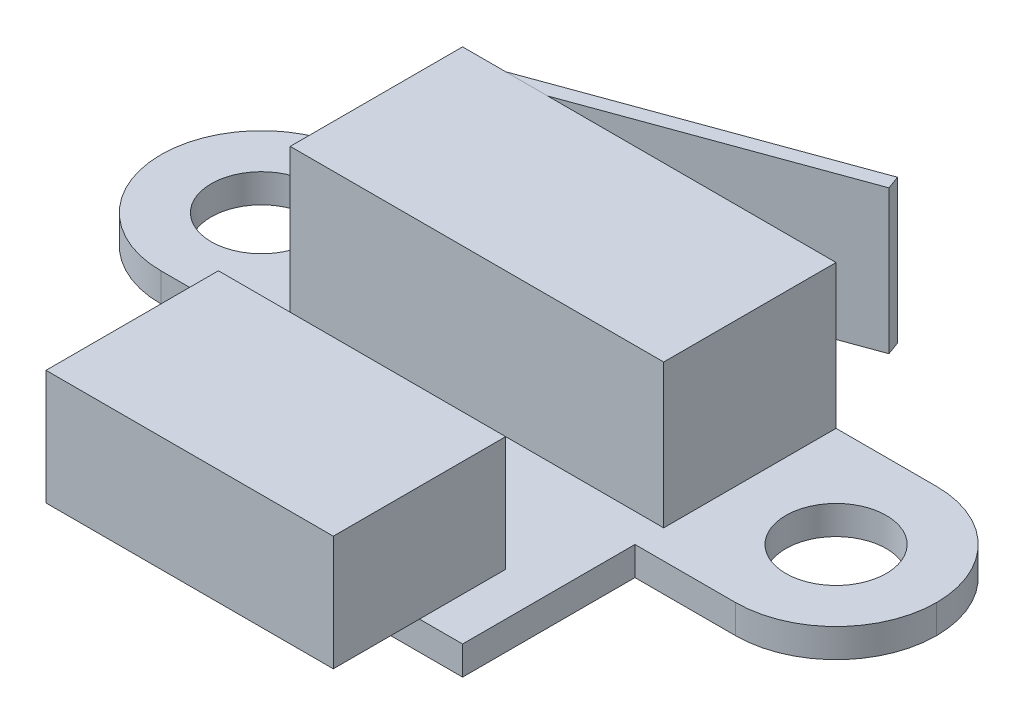
SolidWorks part; units mm, degrees
ref_plane "Front Plane" through (0, 0, 0) normal (0, 0, 1) x (1, 0, 0)
ref_plane "Top Plane" through (0, 0, 0) normal (0, 1, 0) x (1, 0, 0)
ref_plane "Right Plane" through (0, 0, 0) normal (1, 0, 0) x (0, 0, -1)
sketch "Sketch1" plane through (0, 0, 0) normal (0, 1, 0) x (1, 0, 0)
  line L1 (-6.5, -6.5) -> (6.5, -6.5)
  line L2 (-6.5, -6.5) -> (-6.5, 6.5)
  line L3 (-6.5, 6.5) -> (6.5, 6.5)
  line L4 (6.5, -6.5) -> (6.5, 6.5)
  line L5 (-6.5, -6.5) -> (6.5, 6.5) construction
  line L6 (-6.5, 6.5) -> (6.5, -6.5) construction
  point P0 (0, 0)
  dimension "D1" = 13
  dimension "D2" = 13
extrude "Boss-Extrude1" add sketch "Sketch1" along normal blind 1
sketch "Sketch4" plane through (-6.5, 0, 0) normal (-1, 0, 0) x (0, 0, 1)
  line L0 (-6.5, 1) -> (6.5, 1) construction
  line L1 (-6.5, 0) -> (0.5, 0)
  line L2 (-6.5, 0) -> (-6.5, 1)
  line L3 (-6.5, 1) -> (0.5, 1)
  line L4 (0.5, 0) -> (0.5, 1)
  dimension "D1" = 7
extrude "Boss-Extrude2" add sketch "Sketch4" along normal blind 7
sketch "Sketch5" plane through (6.5, 0, 0) normal (1, 0, 0) x (0, 0, -1)
  line L0 (-6.5, 0) -> (6.5, 0) construction
  line L1 (6.5, 1) -> (-0.5, 1)
  line L2 (6.5, 1) -> (6.5, 0)
  line L3 (6.5, 0) -> (-0.5, 0)
  line L4 (-0.5, 1) -> (-0.5, 0)
  dimension "D1" = 7
extrude "Boss-Extrude3" add sketch "Sketch5" along normal blind 7
sketch "Sketch6" plane through (0, 1, 0) normal (0, 1, 0) x (1, 0, 0)
  line L0 (-13.5, -0.5) -> (-6.5, -0.5) construction
  line L2 (-13.5, -0.5) -> (-13.5, 6.5) construction
  circle A0 centre (-10, 3) radius 1.75
  circle A1 centre (10, 3) radius 1.75
  point P10 (13.5, 2.898)
  dimension "D1" = 3.5
  dimension "D4" = 3.5
  dimension "D2" = 3.5
  dimension "D3" = 3.5
  dimension "D5" = 20
extrude "Cut-Extrude1" cut sketch "Sketch6" against normal through all
sketch "Sketch7" plane through (0, 1, 0) normal (0, 1, 0) x (1, 0, 0)
  line L0 (13.5, 6.5) -> (-13.5, 6.5) construction
  line L1 (-5, -3.5) -> (5, -3.5)
  line L2 (-5, -3.5) -> (-5, -9.5)
  line L3 (-5, -9.5) -> (5, -9.5)
  line L4 (5, -3.5) -> (5, -9.5)
  line L5 (-6.5, -0.5) -> (-6.5, -6.5) construction
  dimension "D1" = 6
  dimension "D2" = 10
  dimension "D3" = 10
  dimension "D4" = 1.5
extrude "Boss-Extrude4" add sketch "Sketch7" along normal blind 4
sketch "Sketch8" plane through (0, 1, 0) normal (0, 1, 0) x (1, 0, 0)
  line L0 (-6.5, -0.5) -> (-6.5, -6.5) construction
  line L1 (-6.5, 0.5) -> (6.5, 0.5)
  line L2 (-6.5, 0.5) -> (-6.5, 6.5)
  line L3 (-6.5, 6.5) -> (6.5, 6.5)
  line L4 (6.5, 0.5) -> (6.5, 6.5)
  line L5 (13.5, 6.5) -> (-13.5, 6.5) construction
  dimension "D1" = 13
  dimension "D2" = 0
  dimension "D3" = 6
  dimension "D4" = 0
extrude "Boss-Extrude5" add sketch "Sketch8" along normal blind 5
sketch "Sketch12" plane through (0, 6, 0) normal (0, 1, 0) x (1, 0, 0)
  line L0 (-5, 6.5) -> (5, 10.1397)
  line L1 (6.5, 6.5) -> (-6.5, 6.5) construction
  line L2 (5, 10.1397) -> (5.171, 9.6699)
  line L3 (5.171, 9.6699) -> (-3.5381, 6.5)
  line L4 (-3.5381, 6.5) -> (-5, 6.5)
  dimension "D1" = 20
  dimension "D2" = 1.5
  dimension "D3" = 10
  dimension "D4" = 0.5
extrude "Boss-Extrude7" add sketch "Sketch12" against normal blind 5 separate body
fillet "Fillet1" radius 3.5 4 edges at (13.5, 0.5, -6.5) (13.5, 0.5, 0.5) (-13.5, 0.5, 0.5) (-13.5, 0.5, -6.5)
